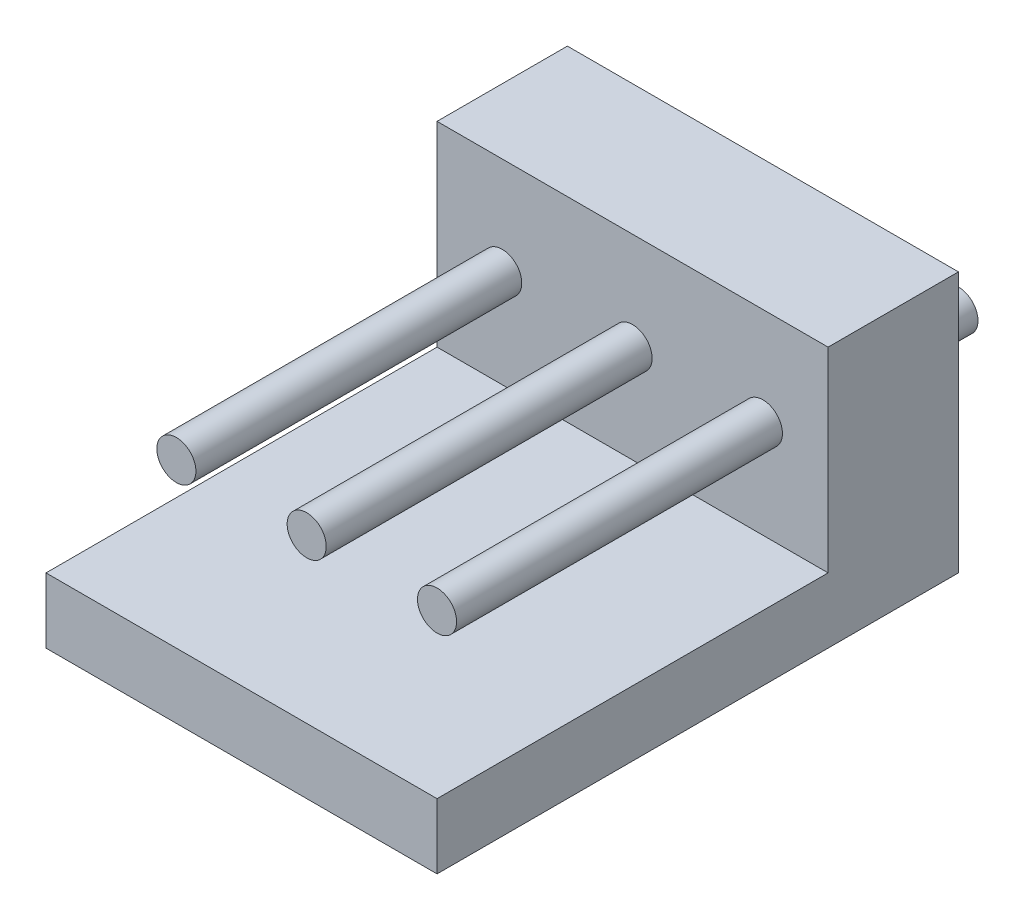
SolidWorks part; units mm, degrees
ref_plane "Спереди" through (0, 0, 0) normal (0, 0, 1) x (1, 0, 0)
ref_plane "Сверху" through (0, 0, 0) normal (0, 1, 0) x (1, 0, 0)
ref_plane "Справа" through (0, 0, 0) normal (1, 0, 0) x (0, 0, -1)
sketch "Эскиз1" plane through (0, 0, 0) normal (0, 0, 1) x (1, 0, 0)
  line L1 (0, 0) -> (15, 0)
  line L2 (0, 0) -> (0, 10)
  line L3 (0, 10) -> (15, 10)
  line L4 (15, 0) -> (15, 10)
  dimension "D1" = 15
  dimension "D2" = 10
extrude "Вытянуть1" add sketch "Эскиз1" along normal blind 5
sketch "Эскиз2" plane through (0, 0, 5) normal (0, 0, 1) x (1, 0, 0)
  line L1 (15, 0) -> (15, 10) construction
  line L2 (0, 0) -> (15, 0)
  line L3 (0, 0) -> (0, 2.5)
  line L4 (0, 2.5) -> (15, 2.5)
  line L7 (15, 0) -> (15, 2.5)
  dimension "D1" = 2.5
extrude "Вытянуть2" add sketch "Эскиз2" along normal blind 15
sketch "Эскиз3" plane through (0, 0, 5) normal (0, 0, 1) x (1, 0, 0)
  line L3 (7.5, 12.0229) -> (7.5, -0.8356) construction
  line L4 (0, 10) -> (0, 2.5) construction
  line L5 (15, 2.5) -> (15, 10) construction
  line L7 (7.5, 6.25) -> (16.9518, 6.25) construction
  line L9 (15, 10) -> (0, 10) construction
  circle A0 centre (7.5, 6.25) radius 0.75
  circle A1 centre (12.5, 6.25) radius 0.75
  circle A2 centre (2.5, 6.25) radius 0.75
  dimension "D1" = 10
  dimension "D2" = 1.5
  dimension "D3" = 3.75
extrude "Вытянуть3" add sketch "Эскиз3" along normal blind 12.5 and the other way blind 7.5
